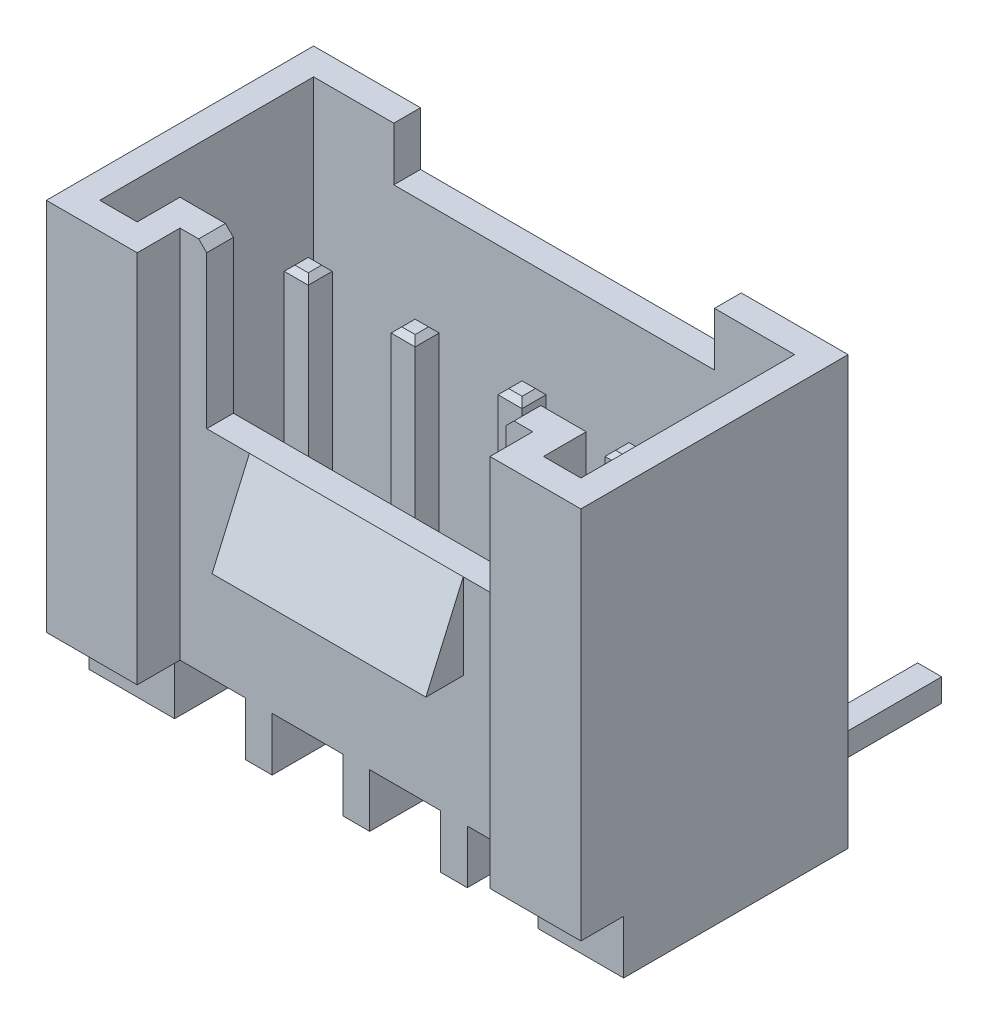
SolidWorks part; units mm, degrees
ref_plane "Plan de face" through (0, 0, 0) normal (0, 0, 1) x (1, 0, 0)
ref_plane "Plan de dessus" through (0, 0, 0) normal (0, 1, 0) x (1, 0, 0)
ref_plane "Plan de droite" through (0, 0, 0) normal (1, 0, 0) x (0, 0, -1)
sketch "Esquisse1" plane through (0, 0, 0) normal (0, 1, 0) x (1, 0, 0)
  line L1 (0, 0) -> (10, 0)
  line L2 (0, 0) -> (0, 5)
  line L3 (0, 5) -> (10, 5)
  line L4 (10, 0) -> (10, 5)
  dimension "D1" = 5
  dimension "D2" = 10
extrude "Boss.-Extru.1" add sketch "Esquisse1" along normal blind 8
sketch "Esquisse2" plane through (0, 8, 0) normal (0, 1, 0) x (1, 0, 0)
  line L0 (0, 0) -> (10, 0) construction
  line L1 (1.7, 0) -> (8.3, 0)
  line L2 (1.7, 0) -> (1.7, 0.8)
  line L3 (1.7, 0.8) -> (8.3, 0.8)
  line L4 (8.3, 0) -> (8.3, 0.8)
  line L5 (0, 5) -> (0, 0) construction
  line L6 (10, 0) -> (10, 5) construction
  dimension "D1" = 1.7
  dimension "D2" = 1.7
  dimension "D3" = 0.8
extrude "Enlèv. mat.-Extru.1" cut sketch "Esquisse2" against normal blind 8
sketch "Esquisse4" plane through (0, 8, 0) normal (0, 1, 0) x (1, 0, 0)
  line L16 (0.5, 0.5) -> (1.2, 0.5)
  line L17 (1.2, 0.5) -> (1.2, 1.3)
  line L18 (1.2, 1.3) -> (8.8, 1.3)
  line L19 (8.8, 1.3) -> (8.8, 0.5)
  line L20 (8.8, 0.5) -> (9.5, 0.5)
  line L21 (9.5, 0.5) -> (9.5, 4.5)
  line L22 (9.5, 4.5) -> (0.5, 4.5)
  line L23 (0.5, 4.5) -> (0.5, 0.5)
  line L24 (0.5, 0.5) -> (1.2, 0.5)
  line L25 (1.2, 0.5) -> (1.2, 1.3)
  line L26 (1.2, 1.3) -> (8.8, 1.3)
  line L27 (8.8, 1.3) -> (8.8, 0.5)
  line L28 (8.8, 0.5) -> (9.5, 0.5)
  line L29 (9.5, 0.5) -> (9.5, 4.5)
  line L30 (9.5, 4.5) -> (0.5, 4.5)
  line L31 (0.5, 4.5) -> (0.5, 0.5)
  dimension "D1" = 0.5
extrude "Enlèv. mat.-Extru.2" cut sketch "Esquisse4" against normal blind 6.5
sketch "Esquisse5" plane through (0, 8, 0) normal (0, 1, 0) x (1, 0, 0)
  line L0 (10, 5) -> (0, 5) construction
  line L1 (2, 5) -> (8, 5)
  line L2 (2, 5) -> (2, 4.5)
  line L3 (2, 4.5) -> (8, 4.5)
  line L4 (8, 5) -> (8, 4.5)
  line L5 (9.5, 4.5) -> (0.5, 4.5) construction
  line L6 (10, 0) -> (10, 5) construction
  line L7 (0, 5) -> (0, 0) construction
  dimension "D1" = 2
  dimension "D2" = 2
extrude "Enlèv. mat.-Extru.3" cut sketch "Esquisse5" against normal blind 1
sketch "Esquisse6" plane through (0, 8, 0) normal (0, 1, 0) x (1, 0, 0)
  line L0 (1.2, 1.3) -> (8.8, 1.3) construction
  line L1 (2.2, 1.3) -> (7.8, 1.3)
  line L2 (2.2, 1.3) -> (2.2, 0.8)
  line L3 (2.2, 0.8) -> (7.8, 0.8)
  line L4 (7.8, 1.3) -> (7.8, 0.8)
  line L5 (8.3, 0.8) -> (1.7, 0.8) construction
  line L6 (10, 0) -> (10, 5) construction
  line L7 (0, 5) -> (0, 0) construction
  dimension "D1" = 2.2
  dimension "D2" = 2.2
extrude "Enlèv. mat.-Extru.4" cut sketch "Esquisse6" against normal blind 3
sketch "Esquisse7" plane through (10, 0, 0) normal (1, 0, 0) x (0, 0, -1)
  line L1 (0, 0) -> (0.8, 0)
  line L2 (0, 0) -> (0, 1)
  line L3 (0, 1) -> (0.8, 1)
  line L4 (0.8, 0) -> (0.8, 1)
  dimension "D1" = 0.8
  dimension "D2" = 1
extrude "Enlèv. mat.-Extru.5" cut sketch "Esquisse7" against normal blind 10
sketch "Esquisse8" plane through (0, 0, 0) normal (0, -1, 0) x (1, 0, 0)
  line L0 (10, -0.8) -> (0, -0.8) construction
  line L1 (1.6, -0.8) -> (8.4, -0.8)
  line L2 (1.6, -0.8) -> (1.6, -5)
  line L3 (1.6, -5) -> (8.4, -5)
  line L4 (8.4, -0.8) -> (8.4, -5)
  line L5 (10, -5) -> (0, -5) construction
  line L6 (0, -5) -> (0, -0.8) construction
  line L7 (10, -0.8) -> (10, -5) construction
  dimension "D1" = 1.6
  dimension "D2" = 1.6
extrude "Enlèv. mat.-Extru.6" cut sketch "Esquisse8" against normal blind 1
sketch "Esquisse9" plane through (1.6, 0, 0) normal (1, 0, 0) x (0, 0, -1)
  line L0 (5, 1) -> (0.8, 1) construction
  line L1 (4.7, 1) -> (3.9, 0.2)
  line L2 (3.9, 0.2) -> (1.9, 0.2)
  line L3 (1.9, 0.2) -> (1.1, 1)
  line L4 (0.8, 0) -> (5, 0) construction
  line L5 (4.7, 1) -> (1.1, 1)
  dimension "D1" = 45
  dimension "D2" = 45
  dimension "D3" = 0.2
  dimension "D4" = 0.3
  dimension "D5" = 0.3
extrude "Boss.-Extru.2" add sketch "Esquisse9" along normal blind 6.8
ref_plane "Plan1" through (5, 0, 0) normal (1, 0, 0) x (0, 0, -1)
sketch "Esquisse11" plane through (5, 0, 0) normal (1, 0, 0) x (0, 0, -1)
  line L0 (0.8, 5) -> (0.1, 3.4)
  line L1 (0.1, 3.4) -> (0.8, 3.4)
  line L2 (0.8, 1) -> (0.8, 8) construction
  line L3 (0.8, 3.4) -> (0.8, 5)
  dimension "D1" = 1.6
  dimension "D2" = 0.7
extrude "Boss.-Extru.3" add sketch "Esquisse11" along normal blind 2 and the other way blind 2
ref_plane "Plan2" through (0, 1, 0) normal (0, 1, 0) x (1, 0, 0)
sketch "Esquisse12" plane through (0, 1, 0) normal (0, 1, 0) x (1, 0, 0)
  line L0 (8.3, 0.8) -> (1.7, 0.8) construction
  line L1 (1.6, 5) -> (8.4, 5) construction
  line L2 (3, 0.8) -> (7, 0.8) construction
  line L3 (4.75, 0.8) -> (5.25, 0.8)
  line L4 (4.75, 0.8) -> (4.75, 5)
  line L5 (4.75, 5) -> (5.25, 5)
  line L6 (5.25, 0.8) -> (5.25, 5)
  line L8 (2.925, 0.8) -> (3.425, 0.8)
  line L9 (2.925, 0.8) -> (2.925, 5)
  line L10 (2.925, 5) -> (3.425, 5)
  line L11 (3.425, 0.8) -> (3.425, 5)
  line L12 (6.575, 0.8) -> (7.075, 0.8)
  line L13 (6.575, 0.8) -> (6.575, 5)
  line L14 (6.575, 5) -> (7.075, 5)
  line L15 (7.075, 0.8) -> (7.075, 5)
  line L16 (3.175, 0.8) -> (3.175, 5) construction
  line L17 (6.825, 0.8) -> (6.825, 5) construction
  point P0 (5, 0.8)
  point P1 (5, 5)
  dimension "D1" = 0.5
  dimension "D2" = 0.25
  dimension "D3" = 0.5
  dimension "D4" = 0.5
  dimension "D5" = 0.25
  dimension "D6" = 0.25
  dimension "D7" = 1.575
  dimension "D8" = 1.575
extrude "Boss.-Extru.4" add sketch "Esquisse12" against normal blind 1
chamfer "Chanfrein1" distance 0.15 angle 45 2 edges at (2.2, 8, -1.05) (7.8, 8, -1.05)
sketch "Esquisse13" plane through (0, 0.2, 0) normal (0, -1, 0) x (1, 0, 0)
  line L0 (5, -0.8) -> (5, -4.5466) construction
  line L1 (3, -0.8) -> (7, -0.8) construction
  line L2 (2.225, -2.9) -> (3.775, -2.9) construction
  line L3 (2.925, -1.9) -> (1.6, -1.9) construction
  line L4 (4.225, -3.125) -> (3.775, -3.125)
  line L5 (4.225, -3.125) -> (4.225, -2.675)
  line L6 (4.225, -2.675) -> (3.775, -2.675)
  line L7 (3.775, -3.125) -> (3.775, -2.675)
  line L8 (2.225, -3.125) -> (1.775, -3.125)
  line L13 (2.225, -3.125) -> (2.225, -2.675)
  line L14 (2.225, -2.675) -> (1.775, -2.675)
  line L16 (1.775, -3.125) -> (1.775, -2.675)
  line L19 (7.775, -3.125) -> (8.225, -3.125)
  line L20 (8.225, -3.125) -> (8.225, -2.675)
  line L21 (7.775, -2.675) -> (8.225, -2.675)
  line L22 (7.775, -3.125) -> (7.775, -2.675)
  line L23 (5.775, -3.125) -> (6.225, -3.125)
  line L24 (6.225, -3.125) -> (6.225, -2.675)
  line L25 (5.775, -2.675) -> (6.225, -2.675)
  line L26 (5.775, -3.125) -> (5.775, -2.675)
  point P14 (0, 0)
  point P15 (0, 0)
  dimension "D1" = 0.45
  dimension "D2" = 1
  dimension "D3" = 2
  dimension "D4" = 2
extrude "Boss.-Extru.5" add sketch "Esquisse13" along normal blind 0.5 and the other way blind 6.3
sketch "Esquisse14" plane through (0, 0, -3.125) normal (0, 0, -1) x (-1, 0, 0)
  line L1 (-7.775, 0.2) -> (-7.775, -0.3) construction
  line L2 (-8.225, -0.3) -> (-7.775, -0.3)
  line L3 (-8.225, -0.3) -> (-8.225, 0.13)
  line L4 (-8.225, 0.13) -> (-7.775, 0.13)
  line L5 (-7.775, -0.3) -> (-7.775, 0.13)
  line L7 (-5.775, -0.3) -> (-5.775, 0.13)
  line L9 (-6.225, -0.3) -> (-5.775, -0.3)
  line L10 (-6.225, -0.3) -> (-6.225, 0.13)
  line L11 (-6.225, 0.13) -> (-5.775, 0.13)
  line L12 (-3.775, -0.3) -> (-3.775, 0.13)
  line L13 (-4.225, -0.3) -> (-3.775, -0.3)
  line L14 (-4.225, -0.3) -> (-4.225, 0.13)
  line L15 (-4.225, 0.13) -> (-3.775, 0.13)
  line L16 (-1.775, -0.3) -> (-1.775, 0.13)
  line L17 (-2.225, -0.3) -> (-1.775, -0.3)
  line L18 (-2.225, -0.3) -> (-2.225, 0.13)
  line L19 (-2.225, 0.13) -> (-1.775, 0.13)
  dimension "D1" = 0.43
  dimension "D2" = 4
extrude "Boss.-Extru.6" add sketch "Esquisse14" along normal blind 5.5
fillet "Congé1" radius 0.1 8 edges at (2, 0.13, -3.125) (2, -0.3, -2.675) (4, 0.13, -3.125) (4, -0.3, -2.675) (6, 0.13, -3.125) (6, -0.3, -2.675) (8, 0.13, -3.125) (8, -0.3, -2.675)
chamfer "Chanfrein2" distance 0.1 angle 45 32 edges at (8, 6.5, -3.125) (8.225, 6.5, -2.9) (8, 6.5, -2.675) (7.775, 6.5, -2.9) (6, 6.5, -3.125) (6.225, 6.5, -2.9) (6, 6.5, -2.675) (5.775, 6.5, -2.9) (4, 6.5, -2.675) (3.775, 6.5, -2.9) (4, 6.5, -3.125) (4.225, 6.5, -2.9) (2, 6.5, -2.675) (1.775, 6.5, -2.9) (2, 6.5, -3.125) (2.225, 6.5, -2.9) (8, 0.13, -8.625) (7.775, -0.085, -8.625) (8, -0.3, -8.625) (8.225, -0.085, -8.625) (6, 0.13, -8.625) (5.775, -0.085, -8.625) (6, -0.3, -8.625) (6.225, -0.085, -8.625) (4, 0.13, -8.625) (3.775, -0.085, -8.625) (4, -0.3, -8.625) (4.225, -0.085, -8.625) (2, 0.13, -8.625) (1.775, -0.085, -8.625) (2, -0.3, -8.625) (2.225, -0.085, -8.625)
